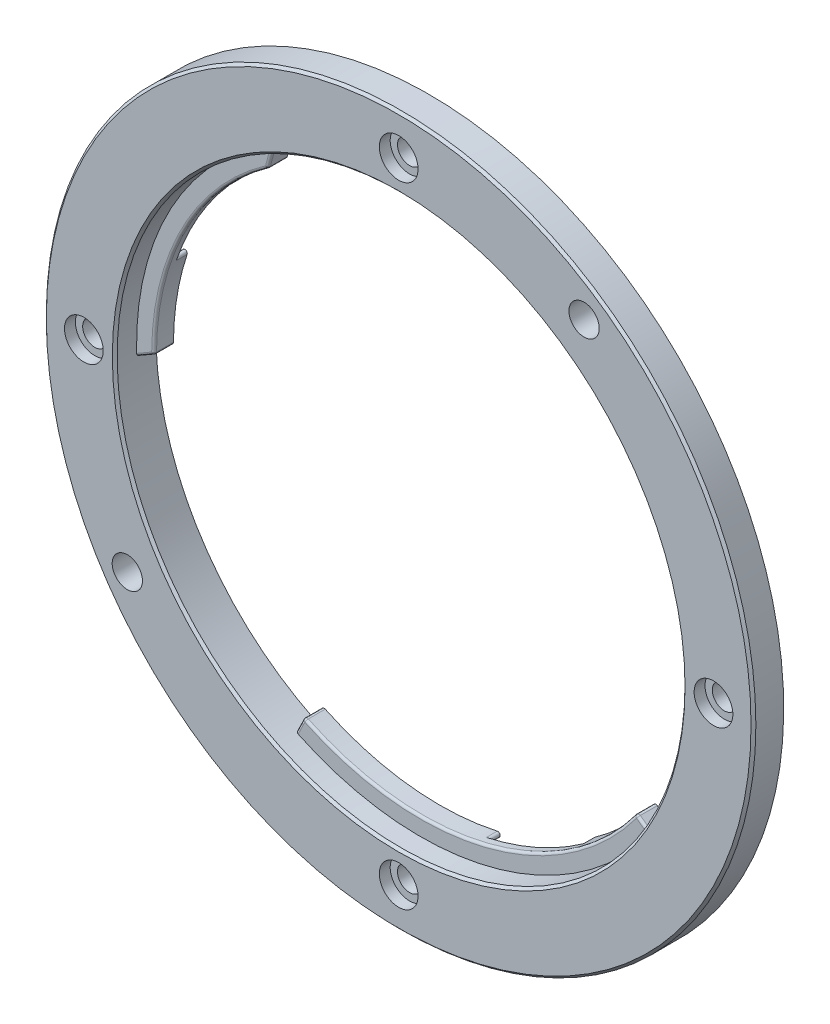
SolidWorks part; units mm, degrees
ref_plane "前视基准面" through (0, 0, 0) normal (0, 0, 1) x (1, 0, 0)
ref_plane "上视基准面" through (0, 0, 0) normal (0, 1, 0) x (1, 0, 0)
ref_plane "右视基准面" through (0, 0, 0) normal (1, 0, 0) x (0, 0, -1)
other "Configuration Table"
sketch "草图1" plane through (0, 0, 0) normal (0, 0, 1) x (1, 0, 0)
  line L0 (0, 0) -> (0, 18.6763) construction
  line L1 (0, 0) -> (17.12, 0) construction
  circle A0 centre (0, 0) radius 23.45
  circle A1 centre (0, 0) radius 29.3
  circle A2 centre (0, 0) radius 26 construction
  circle A3 centre (0, 26) radius 1
  circle A4 centre (-26, 0) radius 1
  circle A5 centre (0, -26) radius 1
  circle A6 centre (26, 0) radius 1
  dimension "D1" = 46.9
  dimension "D2" = 58.6
  dimension "D3" = 52
  dimension "D4" = 2
extrude "凸台-拉伸1" add sketch "草图1" along normal blind 2.5
sketch "草图2" plane through (0, 0, 2.5) normal (0, 0, 1) x (1, 0, 0)
  line L0 (0, 0) -> (-12.8007, 0) construction
  line L1 (0, 0) -> (-22.4107, -14.8333) construction
  line L2 (0, 0) -> (15.311, 22.0871) construction
  circle A0 centre (0, 0) radius 26.875 construction
  circle A1 centre (-22.4107, -14.8333) radius 1.25
  circle A2 centre (15.311, 22.0871) radius 1.25
  dimension "D1" = 53.75
  dimension "D3" = 2.5
  dimension "D4" = 2.5
  dimension "D2" = 33.5
  dimension "D5" = 55.27
extrude "切除-拉伸1" cut sketch "草图2" against normal through all
sketch "草图3" plane through (0, 0, 0) normal (0, 0, -1) x (-1, 0, 0)
  line L0 (50.415, 188.0781) -> (517.0817, 188.0781) construction
  line L1 (0, 0) -> (-18.9714, -13.7836)
  line L2 (0, 0) -> (10.2798, -21.0767)
  line L3 (0, 0) -> (-21.0387, 6.4322) construction
  line L4 (0, 0) -> (-10.6658, 19.2416) construction
  line L5 (0, 0) -> (12.6187, 18.0213) construction
  line L6 (0, 0) -> (22, 0) construction
  line L7 (0, 0) -> (0, -23.45) construction
  line L8 (-21.0387, 6.4322) -> (-22.854, 5.2533)
  line L9 (-10.6658, 19.2416) -> (-9.8901, 21.2624)
  line L10 (12.6187, 18.0213) -> (12.0585, 20.1121)
  line L11 (22, 0) -> (23.4354, -0.8287)
  circle A0 centre (0, 0) radius 23.45
  circle A1 centre (0, 0) radius 23.45 construction
  circle A2 centre (0, 0) radius 22
  circle A3 centre (0, 0) radius 24
  circle M5 centre (0, 0) radius 23.45
  dimension "D1" = 44
  dimension "D12" = 48
  dimension "D2" = 54
  dimension "D3" = 26
  dimension "D4" = 90
  dimension "D5" = 73
  dimension "D6" = 29
  dimension "D7" = 35
  dimension "D8" = 130
  dimension "D9" = 130
  dimension "D10" = 130
  dimension "D11" = 150
extrude "凸台-拉伸2" add sketch "草图3" along normal blind 0.9 and the other way blind 0.7 contours A2 L9 L8 M5 | A2 L11 L10 M5 | A2 L1 L2 M5 | A3 M5 region at (5.3975, -21.6481, 0) region at (17.1603, 13.8961, 0) region at (-19.7257, 10.2685, 0) region at (23.9321, 0, 0)
fillet "圆角1" radius 0.2 15 edges at (-9.6442, -19.7735, -0.1) (17.7984, -12.9313, -0.1) (5.3223, -21.3465, 0.7) (18.3849, -13.3574, 0.7) (-9.962, -20.4251, 0.7) (21.9464, 5.8427, 0.7) (17.0972, 13.845, 0.7) (10.278, 20.252, 0.7) (-22.7177, -0.4144, 0.7) (-19.5142, 10.1585, 0.7) (-12.3386, 19.0667, 0.7) (-12.6187, 18.0213, -0.1) (-22, 0, -0.1) (21.0387, 6.4322, -0.1) (10.6658, 19.2416, -0.1)
chamfer "倒角1" distance 0.2 angle 45 2 edges at (29.3, 0, 2.5) (23.45, 0, 2.5)
sketch "草图4" plane through (0, 0, 2.5) normal (0, 0, 1) x (1, 0, 0)
  circle A0 centre (-26, 0) radius 1.6
  circle A1 centre (0, 26) radius 1.6
  circle A2 centre (26, 0) radius 1.6
  circle A3 centre (0, -26) radius 1.6
  dimension "D1" = 3.2
extrude "切除-拉伸2" cut sketch "草图4" against normal blind 0.9
sketch "草图5" plane through (0, 0, 0) normal (0, 0, -1) x (-1, 0, 0)
  line L0 (0, 0) -> (22.4107, -14.8333) construction
  line L1 (21.9411, -9.7257) -> (26.4118, -12.6848)
  line L2 (17.5256, -16.3968) -> (21.9964, -19.3559)
  circle A0 centre (0, 0) radius 24
  circle A1 centre (0, 0) radius 29.3
  circle A2 centre (0, 0) radius 24 construction
  circle A3 centre (0, 0) radius 29.3 construction
  circle A4 centre (22.4107, -14.8333) radius 1.25 construction
  circle A5 centre (22.4107, -14.8333) radius 1.25 construction
  circle M7 centre (0, 0) radius 24
  circle M8 centre (22.4107, -14.8333) radius 1.25
  circle M10 centre (0, 0) radius 29.3
  dimension "D1" = 8
extrude "切除-拉伸3" cut sketch "草图5" against normal blind 0.6 contours L2 L1 M7 M10 M8 region at (-24.1041, -11.3145, 0)
sketch "草图6" plane through (0, 0, -0.9) normal (0, 0, -1) x (-1, 0, 0)
  line L0 (-15.3227, -17.2052) -> (-17.5597, -22.2297)
  line L1 (-17.5597, -22.2297) -> (-4.7701, -27.924)
  line L2 (-4.7701, -27.924) -> (-2.5331, -22.8995)
  line L3 (-2.5331, -22.8995) -> (-15.3227, -17.2052)
  line L4 (-8.9279, -20.0523) -> (0, 0) construction
  line L5 (0, -1000) -> (0, 49000) construction
  line L6 (-12.3152, 19.4715) -> (-21.3142, 8.7469)
  line L7 (-21.3142, 8.7469) -> (-25.5274, 12.2822)
  line L8 (-25.5274, 12.2822) -> (-16.5284, 23.0068)
  line L9 (-16.5284, 23.0068) -> (-12.3152, 19.4715)
  line L10 (15.5093, 17.0372) -> (22.5093, 4.9128)
  line L11 (22.5093, 4.9128) -> (27.2724, 7.6628)
  line L12 (27.2724, 7.6628) -> (20.2724, 19.7872)
  line L13 (20.2724, 19.7872) -> (15.5093, 17.0372)
  line L14 (-16.8147, 14.1092) -> (0, 0) construction
  line L15 (0, 0) -> (19.0093, 10.975) construction
  circle A0 centre (0, 0) radius 21.95 construction
  point P9 (-16.8147, 14.1092)
  point P11 (-8.9279, -20.0523)
  point P19 (19.0093, 10.975)
  dimension "D4" = 43.9
  dimension "D1" = 14
  dimension "D2" = 5.5
  dimension "D3" = 24
  dimension "D5" = 50
  dimension "D6" = 60
extrude "切除-拉伸7" cut sketch "草图6" against normal blind 0.9
fillet "圆角2" radius 0.2 18 edges at (15.7321, -18.1246, -0.45) (15.3227, -17.2052, -0.45) (2.9424, -23.8189, -0.45) (2.5331, -22.8995, -0.45) (-23.3809, 5.4161, -0.45) (-22.5093, 4.9128, -0.45) (-16.3809, 17.5404, -0.45) (-15.5093, 17.0372, -0.45) (22.0852, 9.3938, -0.45) (21.3142, 8.7469, -0.45) (13.0862, 20.1185, -0.45) (12.3152, 19.4715, -0.45) (17.7675, 12.9736, -0.45) (15.8618, 15.2448, -0.45) (10.2821, -19.4494, -0.45) (7.5736, -20.6553, -0.45) (-19.7505, 9.6912, -0.45) (-18.2681, 12.2588, -0.45)
equation "\"2。5\"=10"
